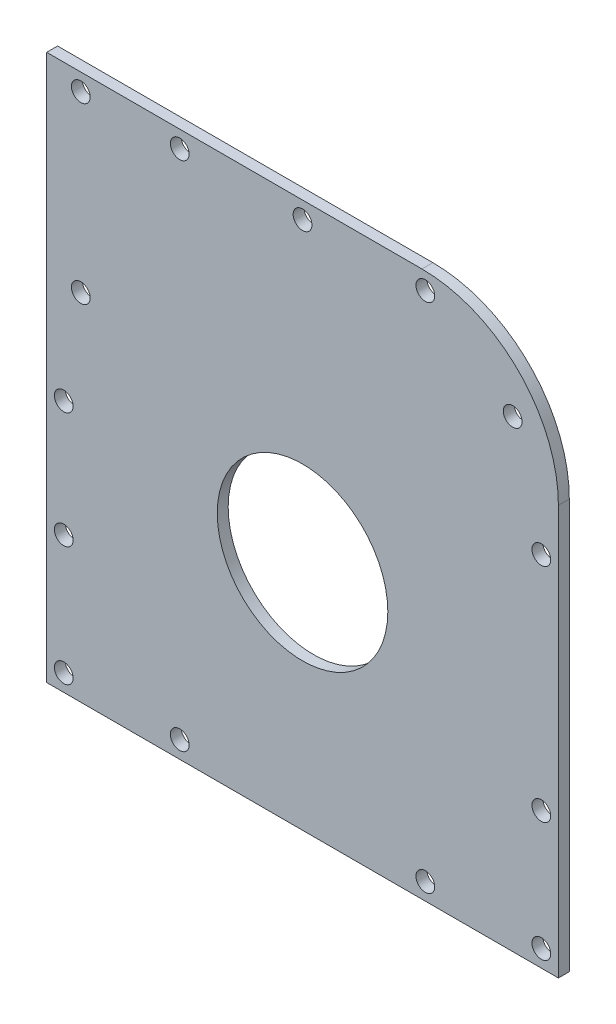
SolidWorks part; units mm, degrees
material "AISI 304"
ref_plane "Front Plane" through (0, 0, 0) normal (0, 0, 1) x (1, 0, 0)
ref_plane "Top Plane" through (0, 0, 0) normal (0, 1, 0) x (1, 0, 0)
ref_plane "Right Plane" through (0, 0, 0) normal (1, 0, 0) x (0, 0, -1)
sketch "Sketch1" plane through (0, 0, 0) normal (0, 0, 1) x (1, 0, 0)
  line L0 (-75, 80) -> (75, -80) construction
  line L1 (-75, 80) -> (75, 80)
  line L2 (-75, 80) -> (-75, -80)
  line L3 (-75, -80) -> (75, -80)
  line L4 (75, 80) -> (75, -80)
  point P0 (0, 0)
  point P6 (0, 0)
  dimension "D1" = 150
  dimension "D2" = 160
extrude "Boss-Extrude1" add sketch "Sketch1" along normal blind 3.2
sketch "Sketch2" plane through (0, 0, 3.2) normal (0, 0, 1) x (1, 0, 0)
  line L0 (0, -12) -> (0, -47.5) construction
  line L3 (-75, -80) -> (75, -80) construction
  circle A1 centre (0, -12) radius 25
  dimension "D1" = 35.5
  dimension "D3" = 25
  dimension "D4" = 68
extrude "Cut-Extrude1" cut sketch "Sketch2" against normal up to next
fillet "Fillet2" radius 40 1 edges at (75, 80, 1.6)
sketch "Sketch4" plane through (0, 0, 3.2) normal (0, 0, 1) x (1, 0, 0)
  line L1 (-75, 68.5917) -> (-2.1136, 63.6666) construction
  line L3 (-15.844, 37.0022) -> (-75, 32.3611) construction
  line L4 (-18.745, 35.9674) -> (-15.844, 37.0022) construction
  spline S1 degree 3 poles (-2.1136, 63.6666) (2.6479, 63.5435) (7.3732, 62.9696) (16.586, 60.9588) (21.0732, 59.5219) (29.6553, 55.8535) (33.75, 53.622) (41.4098, 48.4598) (44.9747, 45.5292) (51.4594, 39.0872) (54.379, 35.5759) (59.4827, 28.1094) (61.6668, 24.1543) (65.2376, 15.9498) (66.6242, 11.7006) (68.5678, 3.0651) (69.1247, -1.321) (69.407, -10.0716) (69.1323, -14.4359) (67.7793, -22.9884) (66.701, -27.1763) (63.7966, -35.2312) (61.9706, -39.0979) (57.6525, -46.38) (55.1604, -49.7953) (49.6136, -56.0632) (46.5591, -58.9158) (40.0087, -63.9697) (36.513, -66.1711) (29.2148, -69.8593) (25.4125, -71.3461) (17.6434, -73.569) (13.6769, -74.3052) (5.7242, -75.0182) (1.7384, -74.9951) (-6.1106, -74.2087) (-9.9735, -73.4455) (-17.4419, -71.2236) (-21.0473, -69.7652) (-27.8787, -66.2219) (-31.1045, -64.1372) (-37.0713, -59.4311) (-39.8121, -56.8099) (-44.7234, -51.1376) (-46.8938, -48.0866) (-50.6012, -41.6745) (-52.1382, -38.3135) (-54.5405, -31.409) (-55.4057, -27.8657) (-56.4508, -20.7276) (-56.6309, -17.133) (-56.3173, -10.0219) (-55.8238, -6.5057) (-54.1987, 0.3254) (-53.0672, 3.64) (-50.224, 9.9549) (-48.5122, 12.955) (-44.5854, 18.5423) (-42.3705, 21.1295) (-37.5304, 25.8099) (-34.9053, 27.9031) (-29.3504, 31.5347) (-26.4206, 33.0731) (-21.867, 34.9417) (-20.3144, 35.493) (-18.745, 35.9674) knots 0 0 0 0 0.03125 0.03125 0.0625 0.0625 0.09375 0.09375 0.125 0.125 0.15625 0.15625 0.1875 0.1875 0.21875 0.21875 0.25 0.25 0.28125 0.28125 0.3125 0.3125 0.34375 0.34375 0.375 0.375 0.40625 0.40625 0.4375 0.4375 0.46875 0.46875 0.5 0.5 0.53125 0.53125 0.5625 0.5625 0.59375 0.59375 0.625 0.625 0.65625 0.65625 0.6875 0.6875 0.71875 0.71875 0.75 0.75 0.78125 0.78125 0.8125 0.8125 0.84375 0.84375 0.875 0.875 0.90625 0.90625 0.9375 0.9375 0.96875 0.96875 0.984535 0.984535 0.984535 0.984535 construction
sketch "Sketch3" plane through (0, 0, 0) normal (0, 0, -1) x (-1, 0, 0)
  line L1 (75, -80) -> (-75, -80) construction
  line L2 (75, 80) -> (75, -80) construction
  line L3 (-75, -80) -> (-75, 40) construction
  line L4 (-35, 80) -> (75, 80) construction
  line L5 (70, 80) -> (70, -80) construction
  circle A0 centre (65, 24) radius 2.75
  circle A1 centre (-70, -75) radius 2.75
  circle A2 centre (36, -75) radius 2.75
  circle A3 centre (-36, -75) radius 2.75
  circle A4 centre (70, -75) radius 2.75
  circle A5 centre (-70, -40) radius 2.75
  circle A6 centre (-70, 25) radius 2.75
  circle A7 centre (-36, 75) radius 2.75
  circle A8 centre (36, 75) radius 2.75
  circle A9 centre (65, 75) radius 2.75
  circle A10 centre (70, -40) radius 2.75
  circle A13 centre (70, -6) radius 2.75
  circle A14 centre (0, 75) radius 2.75
  circle A15 centre (-61.5928, 55.8759) radius 2.75
  dimension "D1" = 5.5
  dimension "D2" = 5.5
  dimension "D3" = 5.5
  dimension "D4" = 5.5
  dimension "D5" = 5.5
  dimension "D6" = 5.5
  dimension "D7" = 5.5
  dimension "D8" = 5.5
  dimension "D9" = 5.5
  dimension "D10" = 5.5
  dimension "D11" = 65
  dimension "D22" = 5.5
  dimension "D36" = 5
  dimension "D12" = 5
  dimension "D13" = 5
  dimension "D14" = 5
  dimension "D15" = 10
  dimension "D16" = 30
  dimension "D17" = 10
  dimension "D18" = 5
  dimension "D19" = 5
  dimension "D20" = 5
  dimension "D21" = 5
  dimension "D23" = 34
  dimension "D24" = 34
  dimension "D25" = 35
  dimension "D26" = 35
  dimension "D27" = 29
  dimension "D28" = 34
  dimension "D31" = 5
  dimension "D32" = 5
  dimension "D33" = 32
  dimension "D34" = 31.9488
  dimension "D35" = 5
extrude "Cut-Extrude2" cut sketch "Sketch3" against normal up to next
